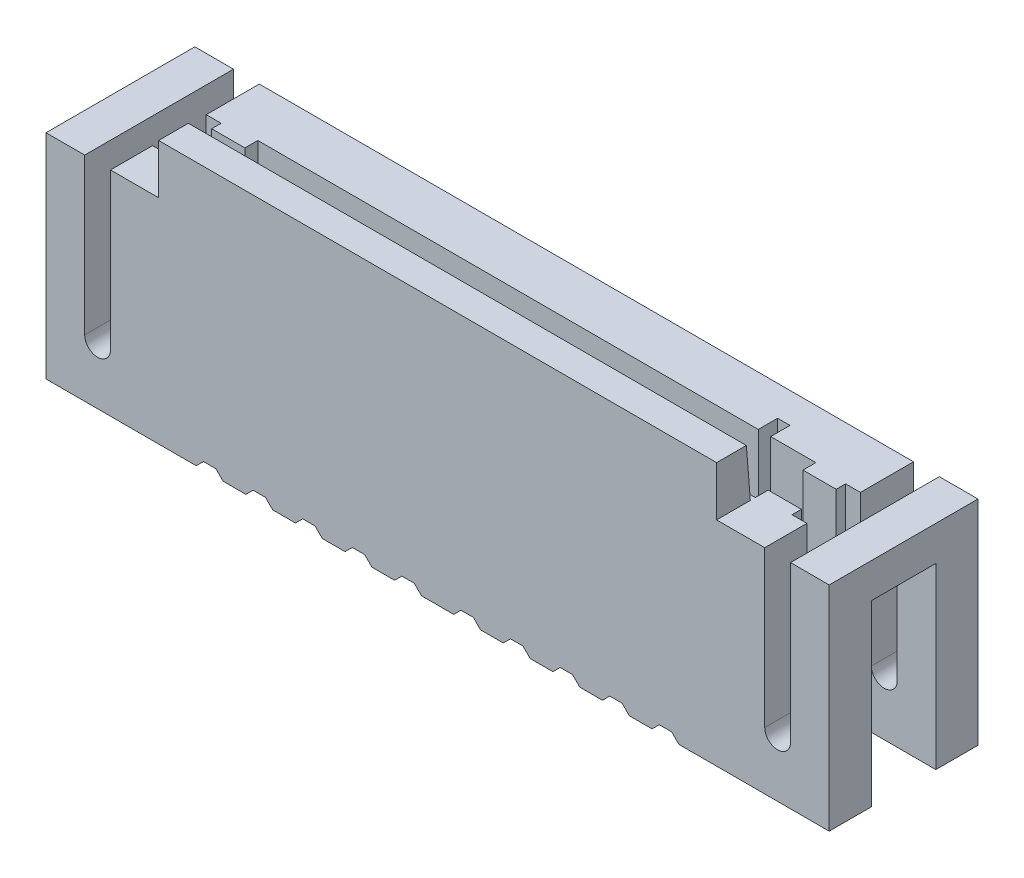
SolidWorks part; units mm, degrees
ref_plane "Płaszczyzna przednia" through (0, 0, 0) normal (0, 0, 1) x (1, 0, 0)
ref_plane "Płaszczyzna górna" through (0, 0, 0) normal (0, 1, 0) x (1, 0, 0)
ref_plane "Płaszczyzna prawa" through (0, 0, 0) normal (1, 0, 0) x (0, 0, -1)
sketch "Sketch1" plane through (0, 0, 0) normal (0, 0, 1) x (1, 0, 0)
  line L0 (4.7291, -2.65) -> (4.875, -2.5041)
  line L1 (4.875, -2.5041) -> (5.125, -2.5041)
  line L2 (5.125, -2.5041) -> (5.2709, -2.65)
  line L3 (5.2709, -2.65) -> (5.7291, -2.65)
  line L4 (5.7291, -2.65) -> (5.875, -2.5041)
  line L5 (5.875, -2.5041) -> (6.125, -2.5041)
  line L6 (6.125, -2.5041) -> (6.2709, -2.65)
  line L7 (6.2709, -2.65) -> (6.7291, -2.65)
  line L8 (6.7291, -2.65) -> (6.875, -2.5041)
  line L9 (6.875, -2.5041) -> (7.125, -2.5041)
  line L10 (7.125, -2.5041) -> (7.2709, -2.65)
  line L11 (7.2709, -2.65) -> (10.3, -2.65)
  line L12 (10.3, -2.65) -> (10.3, 1.65)
  line L13 (10.3, 1.65) -> (9.52, 1.65)
  line L14 (9.52, 1.65) -> (9.52, -1.49)
  line L15 (9, -1.49) -> (9, 1.65)
  line L16 (9, 1.65) -> (8.03, 1.65)
  line L17 (8.03, 1.65) -> (8.03, 2.65)
  line L18 (8.03, 2.65) -> (-8.03, 2.65)
  line L19 (-8.03, 2.65) -> (-8.03, 1.65)
  line L20 (-8.03, 1.65) -> (-9, 1.65)
  line L21 (-9, 1.65) -> (-9, -1.49)
  line L22 (-9.52, -1.49) -> (-9.52, 1.65)
  line L23 (-9.52, 1.65) -> (-10.3, 1.65)
  line L24 (-10.3, 1.65) -> (-10.3, -2.65)
  line L25 (-10.3, -2.65) -> (-7.2709, -2.65)
  line L26 (-7.2709, -2.65) -> (-7.125, -2.5041)
  line L27 (-7.125, -2.5041) -> (-6.875, -2.5041)
  line L28 (-6.875, -2.5041) -> (-6.7291, -2.65)
  line L29 (-6.7291, -2.65) -> (-6.2709, -2.65)
  line L30 (-6.2709, -2.65) -> (-6.125, -2.5041)
  line L31 (-6.125, -2.5041) -> (-5.875, -2.5041)
  line L32 (-5.875, -2.5041) -> (-5.7291, -2.65)
  line L33 (-5.7291, -2.65) -> (-5.2709, -2.65)
  line L34 (-5.2709, -2.65) -> (-5.125, -2.5041)
  line L35 (-5.125, -2.5041) -> (-4.875, -2.5041)
  line L36 (-4.875, -2.5041) -> (-4.7291, -2.65)
  line L37 (-4.7291, -2.65) -> (-4.2709, -2.65)
  line L38 (-4.2709, -2.65) -> (-4.125, -2.5041)
  line L39 (-4.125, -2.5041) -> (-3.875, -2.5041)
  line L40 (-3.875, -2.5041) -> (-3.7291, -2.65)
  line L41 (-3.7291, -2.65) -> (-3.2709, -2.65)
  line L42 (-3.2709, -2.65) -> (-3.125, -2.5041)
  line L43 (-3.125, -2.5041) -> (-2.875, -2.5041)
  line L44 (-2.875, -2.5041) -> (-2.7291, -2.65)
  line L45 (-2.7291, -2.65) -> (-2.2709, -2.65)
  line L46 (-2.2709, -2.65) -> (-2.125, -2.5041)
  line L47 (-2.125, -2.5041) -> (-1.875, -2.5041)
  line L48 (-1.875, -2.5041) -> (-1.7291, -2.65)
  line L49 (-1.7291, -2.65) -> (-1.2709, -2.65)
  line L50 (-1.2709, -2.65) -> (-1.125, -2.5041)
  line L51 (-1.125, -2.5041) -> (-0.875, -2.5041)
  line L52 (-0.875, -2.5041) -> (-0.7291, -2.65)
  line L53 (-0.7291, -2.65) -> (-0.2709, -2.65)
  line L54 (-0.2709, -2.65) -> (-0.125, -2.5041)
  line L55 (-0.125, -2.5041) -> (0.125, -2.5041)
  line L56 (0.125, -2.5041) -> (0.2709, -2.65)
  line L57 (0.2709, -2.65) -> (0.7291, -2.65)
  line L58 (0.7291, -2.65) -> (0.875, -2.5041)
  line L59 (0.875, -2.5041) -> (1.125, -2.5041)
  line L60 (1.125, -2.5041) -> (1.2709, -2.65)
  line L61 (1.2709, -2.65) -> (1.7291, -2.65)
  line L62 (1.7291, -2.65) -> (1.875, -2.5041)
  line L63 (1.875, -2.5041) -> (2.125, -2.5041)
  line L64 (2.125, -2.5041) -> (2.2709, -2.65)
  line L65 (2.2709, -2.65) -> (2.7291, -2.65)
  line L66 (2.7291, -2.65) -> (2.875, -2.5041)
  line L67 (2.875, -2.5041) -> (3.125, -2.5041)
  line L68 (3.125, -2.5041) -> (3.2709, -2.65)
  line L69 (3.2709, -2.65) -> (3.7291, -2.65)
  line L70 (3.7291, -2.65) -> (3.875, -2.5041)
  line L71 (3.875, -2.5041) -> (4.125, -2.5041)
  line L72 (4.125, -2.5041) -> (4.2709, -2.65)
  line L73 (4.2709, -2.65) -> (4.7291, -2.65)
  arc A0 (9, -1.49) -> (9.52, -1.49) centre (9.26, -1.49) ccw
  arc A1 (-9.52, -1.49) -> (-9, -1.49) centre (-9.26, -1.49) ccw
extrude "Boss-Extrude1" add sketch "Sketch1" along normal blind 3
sketch "Sketch2" plane through (8.03, 0, 0) normal (1, 0, 0) x (0, 0, -1)
  line L0 (-3, 2.65) -> (-2.4, 2.65) construction
  line L1 (-3, 2.65) -> (0, 2.65) construction
  line L2 (-3, 1.65) -> (-2.32, 1.65) construction
  line L3 (-3, 1.65) -> (0, 1.65) construction
  line L4 (-2.4, 2.65) -> (-2.32, 1.65)
  line L5 (-2.32, 1.65) -> (0.2084, 1.65)
  line L6 (0.2084, 1.65) -> (0.2477, 2.9084)
  line L7 (0.2477, 2.9084) -> (-2.4, 2.65)
extrude "Cut-Extrude1" cut sketch "Sketch2" against normal through all
sketch "Sketch3" plane through (0, 1.65, 0) normal (0, 1, 0) x (1, 0, 0)
  line L0 (8.03, -2.32) -> (8.03, -2.22) construction
  line L1 (8.03, -2.22) -> (8.03, -1)
  line L2 (8.03, -1) -> (-8.03, -1)
  line L3 (8.03, -2.22) -> (-8.03, -2.22)
  line L4 (-8.03, -2.22) -> (-8.03, -1)
extrude "Cut-Extrude2" cut sketch "Sketch3" against normal blind 3
sketch "Sketch4" plane through (0, 1.65, 0) normal (0, 1, 0) x (1, 0, 0)
  line L0 (8.03, -1.1838) -> (7.12, -1.1838) construction
  line L1 (8.03, -2.22) -> (8.03, -1) construction
  line L2 (7.12, -1) -> (7.12, -0.61)
  line L3 (8.03, -1) -> (-8.03, -1) construction
  line L4 (7.12, -1) -> (7.12, -1.06)
  line L5 (7.12, -1.06) -> (6.87, -1.06)
  line L6 (6.87, -1.06) -> (6.87, -0.61)
  line L7 (6.87, -0.61) -> (7.12, -0.61)
  dimension "D1" = 0.91
  dimension "D2" = 0.39
  dimension "D3" = 0.06
extrude "Cut-Extrude3" cut sketch "Sketch4" against normal through all and the other way through all
sketch "Sketch5" plane through (-10.3, 0, 0) normal (-1, 0, 0) x (0, 0, 1)
  line L0 (1.5, -2.65) -> (1.5, 0.95) construction
  line L1 (3, -2.65) -> (0, -2.65) construction
  line L2 (0.85, 0.95) -> (2.15, 0.95)
  line L3 (0.85, 0.95) -> (0.85, -2.65)
  line L4 (2.15, 0.95) -> (2.15, -2.65)
  line L5 (0.85, -2.65) -> (2.15, -2.65)
  dimension "D1" = 3.6
  dimension "D2" = 1.3
extrude "Cut-Extrude4" cut sketch "Sketch5" against normal blind 1.6
ref_plane "Plane7" through (0, 0, 0) normal (-1, 0, 0) x (0, 0, 1)
sketch "Sketch6" plane through (10.3, 0, 0) normal (1, 0, 0) x (0, 0, -1)
  line L0 (-2.15, 0.95) -> (-0.85, 0.95) construction
  line L1 (-2.15, 0.95) -> (-0.85, 0.95)
  line L2 (-2.15, -1.49) -> (-2.15, 0.95) construction
  line L3 (-0.85, 0.95) -> (-0.85, -1.49) construction
  line L4 (-2.15, -1.49) -> (-2.15, 0.95)
  line L5 (-0.85, 0.95) -> (-0.85, -1.49)
  line L6 (-2.15, -1.49) -> (-2.15, -2.65)
  line L7 (-0.85, -1.49) -> (-0.85, -2.65)
  line L8 (-0.85, -2.65) -> (-2.15, -2.65)
extrude "Cut-Extrude5" cut sketch "Sketch6" against normal blind 1.6
sketch "Sketch8" plane through (-8.7, 0, 0) normal (-1, 0, 0) x (0, 0, 1)
  line L0 (2.15, -1.35) -> (2.15, -2.65)
  line L1 (2.15, -2.65) -> (2.15, 0.95) construction
  line L2 (1, -1.35) -> (2.22, -1.35) construction
  line L3 (2.15, -2.65) -> (1.85, -2.65)
  line L4 (0.85, -2.65) -> (2.15, -2.65) construction
  line L5 (1.85, -2.65) -> (1.85, -1.35)
  line L6 (1.85, -1.35) -> (2.15, -1.35)
extrude "Boss-Extrude3" add sketch "Sketch8" along normal blind 0.3
sketch "Sketch9" plane through (0, 1.65, 0) normal (0, 1, 0) x (1, 0, 0)
  line L0 (-8.03, -1.61) -> (-9, -1.61) construction
  line L1 (-8.03, -1) -> (-8.03, -2.22) construction
  line L2 (-9, -3) -> (-9, 0) construction
  line L3 (-9, -1.26) -> (-9, -1.96)
  line L4 (-9, -1.26) -> (-8.03, -1.26)
  line L5 (-8.03, -1) -> (-8.03, -2.22) construction
  line L6 (-9, -1.96) -> (-8.03, -1.96)
  line L7 (-8.03, -1.96) -> (-8.03, -1.26)
  dimension "D1" = 0.7
extrude "Cut-Extrude6" cut sketch "Sketch9" against normal up to surface (3 mm away) up to face at (3.4975, -1.35, 1.32)
mirror "Mirror2" about plane through (0, 0, 0) normal (-1, 0, 0) of "Cut-Extrude6"
sketch "Sketch10" plane through (-9, 0, 0) normal (-1, 0, 0) x (0, 0, 1)
  line L0 (0.85, 0.95) -> (2.15, 0.95)
  line L1 (2.15, 0.95) -> (2.15, 1.9451)
  line L2 (2.15, 1.9451) -> (0.85, 1.9451)
  line L3 (0.85, 1.9451) -> (0.85, 0.95)
extrude "Cut-Extrude7" cut sketch "Sketch10" against normal up to surface (0.3 mm away) up to face at (-8.7, -1.0167, 1.32)
sketch "Sketch11" plane through (9, 0, 0) normal (1, 0, 0) x (0, 0, -1)
  line L0 (-2.15, 0.95) -> (-0.85, 0.95)
  line L1 (-0.85, 0.95) -> (-0.85, 2.2899)
  line L2 (-0.85, 2.2899) -> (-2.15, 2.2899)
  line L3 (-2.15, 2.2899) -> (-2.15, 0.95)
extrude "Cut-Extrude8" cut sketch "Sketch11" against normal up to surface (0.3 mm away) up to face at (8.7, -0.525, 1.555)
sketch "Sketch12" plane through (-8.7, 0, 0) normal (-1, 0, 0) x (0, 0, 1)
  line L0 (0.85, -0.65) -> (1.07, -0.65)
  line L1 (0.85, 0.95) -> (0.85, -2.65) construction
  line L2 (1.07, -0.65) -> (1.07, 1.65)
  line L3 (3, 1.65) -> (0, 1.65) construction
  line L4 (1.07, 1.65) -> (0.85, 1.65)
  line L5 (0.85, 1.65) -> (0.85, -0.65)
  dimension "D1" = 0.22
  dimension "D2" = 2.3
extrude "Boss-Extrude4" add sketch "Sketch12" along normal blind 0.3
mirror "Mirror4" about plane through (0, 0, 0) normal (-1, 0, 0) of "Boss-Extrude4"
mirror "Mirror5" about plane through (0, 0, 0) normal (-1, 0, 0) of "Boss-Extrude3"
sketch "Szkic1" plane through (0, 0, 3) normal (0, 0, 1) x (1, 0, 0)
  line L0 (0, 2.65) -> (0, -2.9408) construction
  line L1 (8.03, 2.65) -> (-8.03, 2.65) construction
  line L3 (-2.405, -3.455) -> (2.405, -3.455)
  line L4 (-2.405, -3.455) -> (-2.405, 3.1642)
  line L5 (-2.405, 3.1642) -> (2.405, 3.1642)
  line L6 (2.405, -3.455) -> (2.405, 3.1642)
  line L7 (-2.405, -3.455) -> (2.405, 3.1642) construction
  line L8 (-2.405, 3.1642) -> (2.405, -3.455) construction
  point P5 (0, -0.1454)
  dimension "D1" = 4.81
extrude "Wytnij-wyciągnięcie1" cut sketch "Szkic1" against normal through all and the other way through all
move or copy body "Obiekt-Przenieś/Kopiuj1" bodies to move or copy 150 copy no translate (4.81, 0, 0) parameters "D1"=4.81, "D2"=0, "D3"=0
combine bodies "Połącz1" operation type add bodies to combine 151 149
